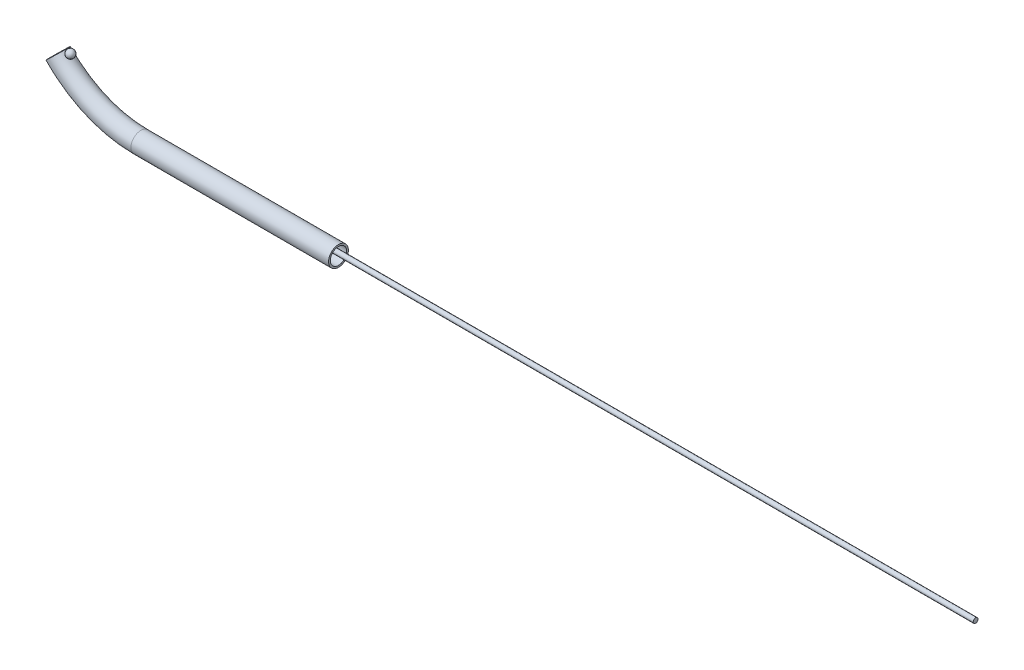
SolidWorks part; units mm, degrees
ref_plane "Front Plane" through (0, 0, 0) normal (0, 0, 1) x (1, 0, 0)
ref_plane "Top Plane" through (0, 0, 0) normal (0, 1, 0) x (1, 0, 0)
ref_plane "Right Plane" through (0, 0, 0) normal (1, 0, 0) x (0, 0, -1)
ref_axis "Axis1" through (-88.99, 0, 0) along (1, 0, 0)
sketch "Sketch4" plane through (0, 0, 0) normal (0, 0, 1) x (1, 0, 0)
  line L0 (-218.053, 283.5718) -> (61.923, 683.419) construction
  line L1 (-68.365, 0) -> (-65.9542, 0)
  arc A0 (-68.365, 0) -> (-73.5499, 2.2253) centre (-68.365, 7.1532) cw
  point P2 (-73.5499, 2.2253)
  point P3 (-68.365, 0)
sketch "Sketch1" plane through (0, 0, 0) normal (1, 0, 0) x (0, 0, -1)
  circle A0 centre (0, 0) radius 0.61
  circle A1 centre (0, 0) radius 0.39
  dimension "D1" = 1.22
  dimension "D2" = 0.22
extrude "Boss-Extrude1" [suppressed] add sketch "Sketch1" along normal blind 10
ref_plane "Plane1" through (-65.9542, 0, 0) normal (1, 0, 0) x (0, 0, -1)
sketch "Sketch5" plane through (-65.9542, 0, 0) normal (1, 0, 0) x (0, 0, -1)
  circle A0 centre (0, 0) radius 0.6223
  circle A1 centre (0, 0) radius 0.5143
  dimension "D1" = 1.2446
  dimension "D2" = 1.0287
sweep "Sweep2" add profiles "Sketch5" path "Sketch4"
extrude "Boss-Extrude2" add sketch "Sketch5<2>" along normal blind 10
sketch "Sketch5<2>" plane through (-65.9542, 0, 0) normal (1, 0, 0) x (0, 0, -1) same geometry as "Sketch5"
sketch "Sketch6" plane through (0, 0, 0) normal (0, 0, 1) x (1, 0, 0)
  line L0 (-72.7874, 2.8286) -> (-72.7874, 2.3286) construction
  line L1 (-72.9491, 2.3879) -> (-72.6257, 2.7693)
  circle A0 centre (-72.7874, 2.5786) radius 0.25 construction
  arc A1 (-72.9491, 2.3879) -> (-72.6257, 2.7693) centre (-72.7874, 2.5786) ccw
  dimension "D1" = 0.5
revolve "Revolve2" add sketch "Sketch6" angle 360 about L1
sketch "Sketch7" plane through (0, 0, 0) normal (0, 0, 1) x (1, 0, 0)
  line L0 (-68.365, -0.6223) -> (-55.9542, -0.6223) construction
  line L1 (-68.365, -0.6223) -> (-55.9542, -0.6223) construction
  line L2 (-68.365, 0.1777) -> (-55.9542, 0.1777)
  arc A1 (-74.001, 1.7966) -> (-68.365, -0.6223) centre (-68.365, 7.1532) ccw construction
  arc A2 (-74.001, 1.7966) -> (-68.365, -0.6223) centre (-68.365, 7.1532) ccw construction
  arc A3 (-73.4211, 2.3477) -> (-68.365, 0.1777) centre (-68.365, 7.1532) ccw
  dimension "D1" = 0.8
sketch "Sketch8" plane through (-36.0182, 37.8966, 0) normal (-0.6889, 0.7248, 0) x (0.7248, 0.6889, 0)
  circle A0 centre (-51.6014, 0) radius 0.15
  point P0 (-51.6014, 0)
  dimension "D1" = 0.3
sweep "Sweep3" add profiles "Sketch8" path "Sketch7"
sketch "Sketch9" plane through (-55.9542, 0, 0) normal (1, 0, 0) x (0, 0, -1)
  circle A0 centre (0, 0.1777) radius 0.15 construction
  circle A1 centre (0, 0.1777) radius 0.15
extrude "Boss-Extrude3" add sketch "Sketch9" along normal blind 40
sketch "Sketch11" plane through (-15.9542, 0, 0) normal (1, 0, 0) x (0, 0, -1)
  circle A0 centre (0, 0.1777) radius 0.15 construction
  circle A1 centre (0, 0.1777) radius 0.15
sketch "Sketch10" plane through (-32.5249, 0, 0) normal (0, 0.9916, 0.129) x (1, 0, 0)
  line L1 (16.5707, 0) -> (17.0707, 0)
  line L2 (16.5707, -0.7366) -> (16.5707, 0.7366) construction
  line L3 (19.5707, -2.5) -> (19.5707, -2.6379)
  arc A0 (19.5707, -2.5) -> (17.0707, 0) centre (17.0707, -2.5) ccw
  point P6 (19.5707, 0)
  dimension "D1" = 3
  dimension "D2" = 2.5
